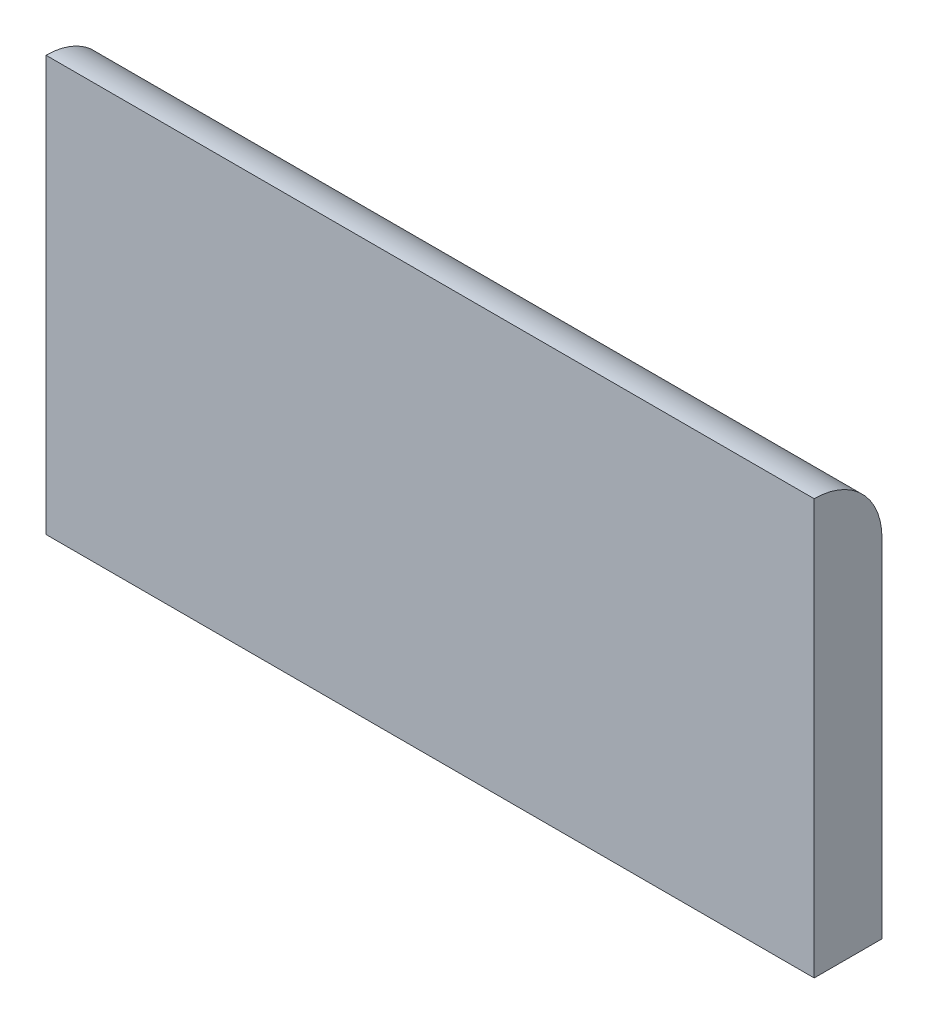
SolidWorks part; units mm, degrees
ref_plane "Front Plane" through (0, 0, 0) normal (0, 0, 1) x (1, 0, 0)
ref_plane "Top Plane" through (0, 0, 0) normal (0, 1, 0) x (1, 0, 0)
ref_plane "Right Plane" through (0, 0, 0) normal (1, 0, 0) x (0, 0, -1)
sketch "Sketch8" plane through (0, 0, 0) normal (0, 0, 1) x (1, 0, 0)
  line L1 (-92.5936, 54.9639) -> (20.7064, 54.9639)
  line L2 (-92.5936, 54.9639) -> (-92.5936, -6.2546)
  line L3 (-92.5936, -6.2546) -> (20.7064, -6.2546)
  line L4 (20.7064, 54.9639) -> (20.7064, -6.2546)
extrude "Boss-Extrude6" add sketch "Sketch8" along normal blind 10
fillet "Fillet7" radius 10 1 edges at (-35.9436, 54.9639, 0)
